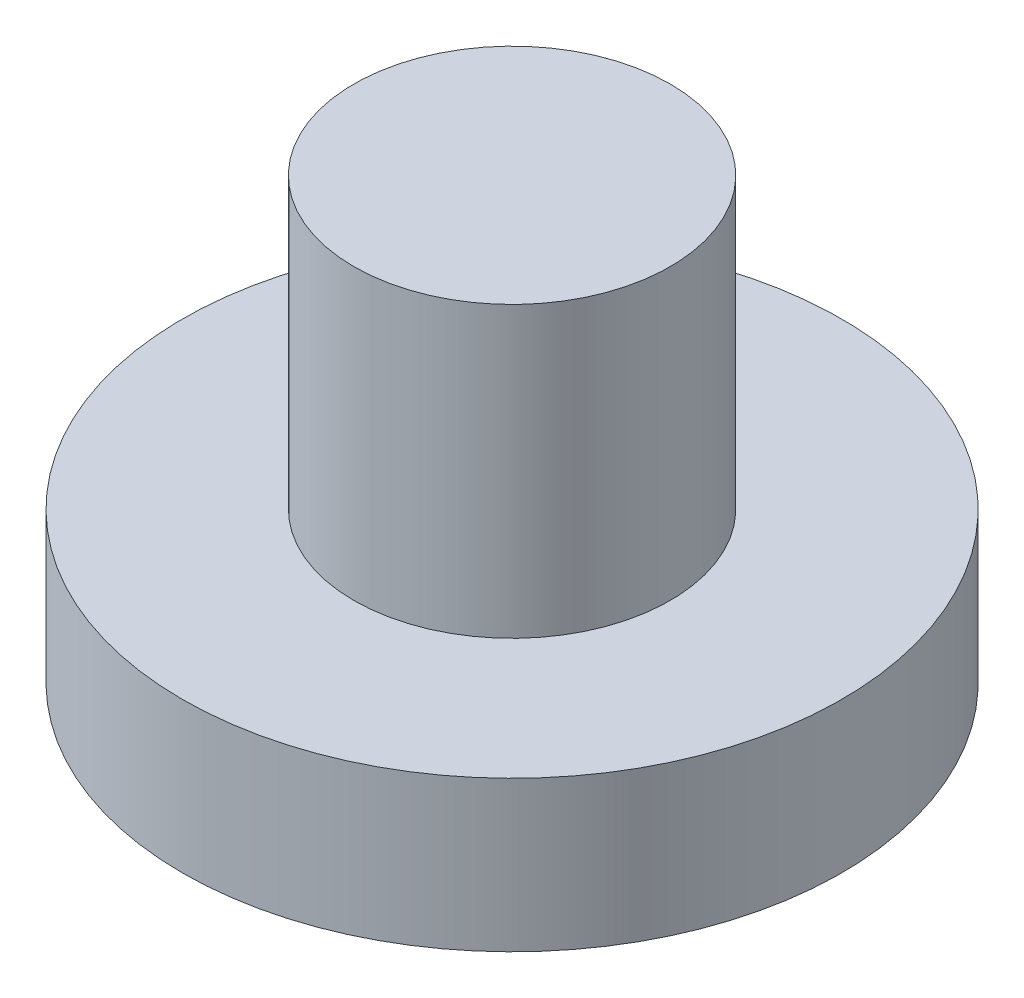
SolidWorks part; units mm, degrees
ref_plane "Front Plane" through (0, 0, 0) normal (0, 0, 1) x (1, 0, 0)
ref_plane "Top Plane" through (0, 0, 0) normal (0, 1, 0) x (1, 0, 0)
ref_plane "Right Plane" through (0, 0, 0) normal (1, 0, 0) x (0, 0, -1)
sketch "Sketch1" plane through (0, 0, 0) normal (0, 1, 0) x (1, 0, 0)
  circle A0 centre (0, 0) radius 7.5
  circle A1 centre (0, 0) radius 3.6
  dimension "D1" = 7.2
  dimension "D2" = 15
extrude "Boss-Extrude1" add sketch "Sketch1" along normal blind 3.42
extrude "Boss-Extrude2" add sketch "Sketch1<2>" along normal blind 10 contours A1 region at (0, 0, 0)
sketch "Sketch1<2>" plane through (0, 0, 0) normal (0, 1, 0) x (1, 0, 0) same geometry as "Sketch1"
